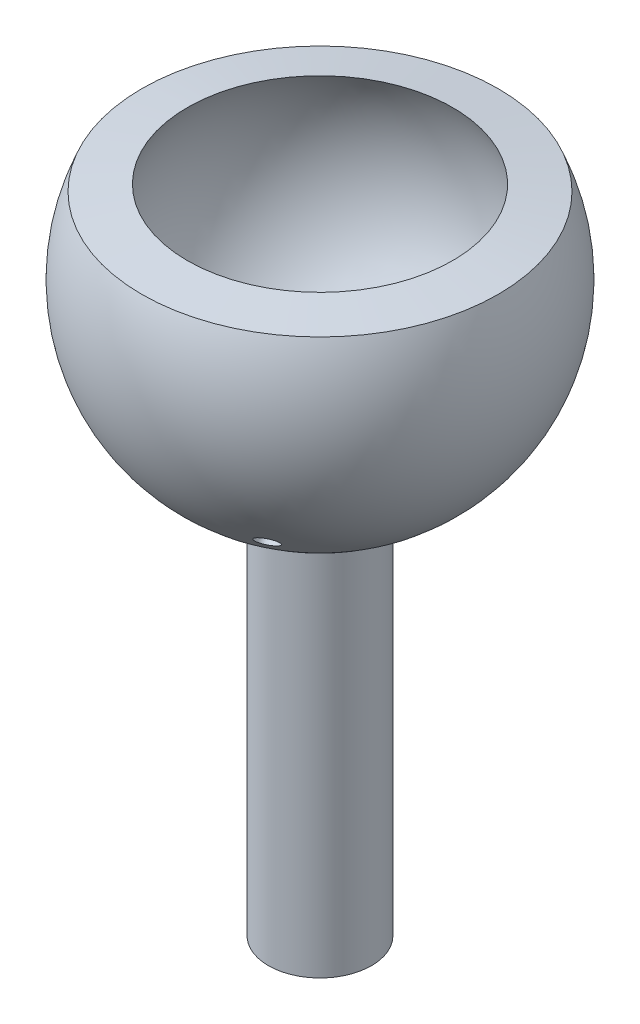
SolidWorks part; units mm, degrees
ref_plane "Front Plane" through (0, 0, 0) normal (0, 0, 1) x (1, 0, 0)
ref_plane "Top Plane" through (0, 0, 0) normal (0, 1, 0) x (1, 0, 0)
ref_plane "Right Plane" through (0, 0, 0) normal (1, 0, 0) x (0, 0, -1)
sketch "Sketch1" plane through (0, 0, 0) normal (0, 0, 1) x (1, 0, 0)
  line L0 (0, 0) -> (-40.53, 25.2022)
  line L1 (0, 0) -> (40.53, 25.2022)
  line L2 (-32.6785, 20.32) -> (32.6785, 20.32) construction
  line L3 (0, 47.7266) -> (0, -47.7266)
  line L4 (-43.8967, 18.7325) -> (43.8967, 18.7325) construction
  line L5 (0, -38.481) -> (12.7, -38.481)
  line L6 (0, -38.481) -> (0, -140.081)
  line L7 (0, -140.081) -> (12.7, -140.081)
  line L8 (12.7, -38.481) -> (12.7, -140.081)
  line L9 (-32.6785, 20.32) -> (-43.8967, 18.7325)
  line L10 (32.6785, 20.32) -> (43.8967, 18.7325)
  circle A0 centre (0, 0) radius 38.481
  circle A1 centre (0, 0) radius 47.7266
  dimension "D1" = 76.962
  dimension "D2" = 95.4532
  dimension "D3" = 12.7
  dimension "D4" = 20.32
  dimension "D5" = 101.6
  dimension "D6" = 1.5875
revolve "Revolve1" add sketch "Sketch1" angle 360 about L3 region at (38.1731, 18.7172, 0) region at (6.1409, -42.8342, 0) region at (6.3695, -93.6177, 0)
sketch "Sketch2" plane through (0, -140.081, 0) normal (0, -1, 0) x (1, 0, 0)
  circle A0 centre (0, 0) radius 2.54
  dimension "D1" = 5.08
extrude "Cut-Extrude1" cut sketch "Sketch2" against normal up to next
hole_wizard "#7 (0.201) Diameter Hole1" positions "3DSketch4" profile "Sketch5" hole size "#7" standard "ANSI Inch" end condition up to next
sketch3d "3DSketch4"
  line L0 (0, 0, 0) -> (0, -31.75, 0) construction
  point P0 (-35.6338, -31.75, 0)
  point P11 (0, 0, 0)
  dimension "D1" = 31.75
sketch "Sketch5" plane through (-35.6338, -31.75, 0) normal (0, 0, 1) x (0.6652, -0.7466, 0)
  line L0 (0, 0) -> (0, 100.4931)
  line L1 (0, 100.4931) -> (2.5527, 100.4931)
  line L2 (2.5527, 100.4931) -> (2.5527, 0)
  line L5 (2.5527, 0) -> (0, 0)
  line L11 (0, -6.35) -> (0, 107.95) construction
  dimension "Thru Hole Dia." = 5.1054
  dimension "Thru Hole Depth" = 100.4931
pattern_circular "CirPattern1" count 3 over 360 about axis through (0, 18.7325, 0) along (0, 1, 0) of "#7 (0.201) Diameter Hole1"
